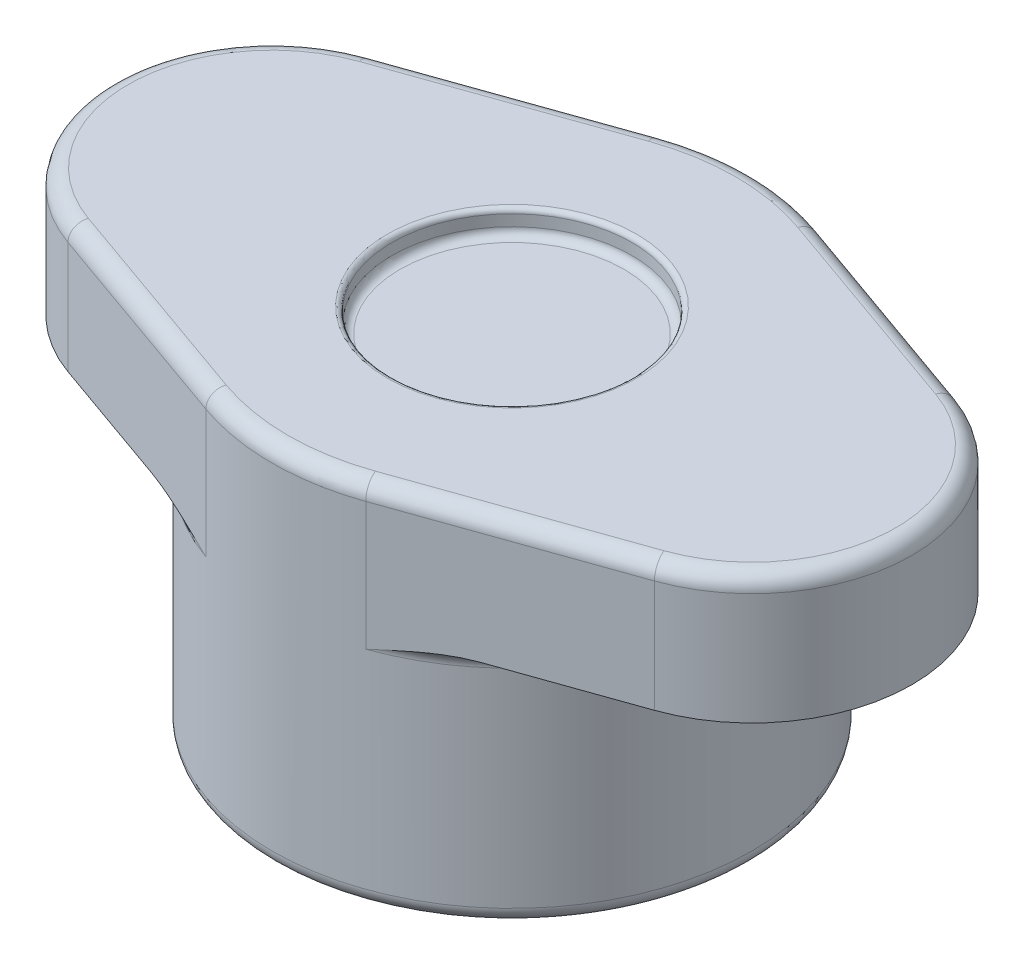
SolidWorks part; units mm, degrees
ref_plane "Front Plane" through (0, 0, 0) normal (0, 0, 1) x (1, 0, 0)
ref_plane "Top Plane" through (0, 0, 0) normal (0, 1, 0) x (1, 0, 0)
ref_plane "Right Plane" through (0, 0, 0) normal (1, 0, 0) x (0, 0, -1)
sketch "Sketch1" plane through (0, 0, 0) normal (0, 1, 0) x (1, 0, 0)
  circle A0 centre (0, 0) radius 15
  dimension "D1" = 30
extrude "Boss-Extrude1" add sketch "Sketch1" along normal blind 15
sketch "Sketch2" plane through (0, 15, 0) normal (0, 1, 0) x (1, 0, 0)
  line L0 (-18.3333, -9.4281) -> (-5, -14.1421)
  line L1 (-29.9387, 0) -> (29.7565, 0) construction
  line L2 (0, 19.632) -> (0, -23.2174) construction
  line L3 (18.3333, -9.4281) -> (5, -14.1421)
  line L4 (-18.3333, 9.4281) -> (-5, 14.1421)
  line L5 (18.3333, 9.4281) -> (5, 14.1421)
  circle A0 centre (0, 0) radius 15 construction
  arc A1 (-5, -14.1421) -> (5, -14.1421) centre (0, 0) ccw
  arc A2 (-18.3333, 9.4281) -> (-18.3333, -9.4281) centre (-15, 0) ccw
  arc A3 (18.3333, -9.4281) -> (18.3333, 9.4281) centre (15, 0) ccw
  arc A4 (5, 14.1421) -> (-5, 14.1421) centre (0, 0) ccw
  dimension "D1" = 20
extrude "Boss-Extrude2" add sketch "Sketch2" along normal blind 8
sketch "Sketch3" plane through (0, 23, 0) normal (0, 1, 0) x (1, 0, 0)
  circle A1 centre (0, 0) radius 7.5
  dimension "D1" = 15
extrude "Cut-Extrude1" cut sketch "Sketch3" against normal blind 1.5
fillet "Fillet1" radius 0.5 1 edges at (0, 21.5, 7.5)
fillet "Fillet2" radius 1 11 edges at (-11.6667, 23, 11.7851) (-25, 23, 0) (-11.6667, 23, -11.7851) (11.6667, 23, -11.7851) (25, 23, 0) (11.6667, 23, 11.7851) (0, 0, 15) (0, 23, -15) (0, 23, 15)
fillet "Fillet3" radius 0.3 1 edges at (0, 23, 7.5)
